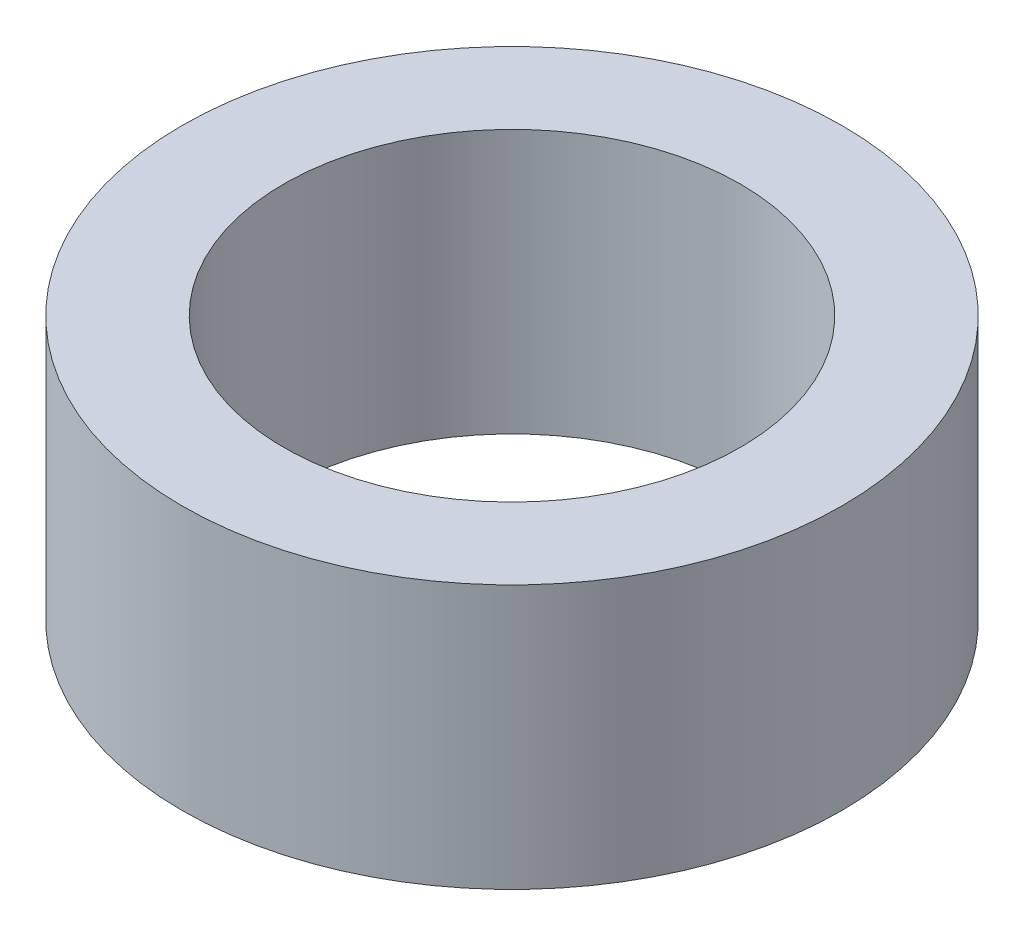
SolidWorks part; units mm, degrees
ref_plane "Front Plane" through (0, 0, 0) normal (0, 0, 1) x (1, 0, 0)
ref_plane "Top Plane" through (0, 0, 0) normal (0, 1, 0) x (1, 0, 0)
ref_plane "Right Plane" through (0, 0, 0) normal (1, 0, 0) x (0, 0, -1)
sketch "Sketch1" plane through (0, 0, 0) normal (0, 1, 0) x (1, 0, 0)
  circle A0 centre (0, 0) radius 32.5
  dimension "FLANGE_OD" = 65
extrude "Boss-Extrude1" add sketch "Sketch1" along normal blind 26
sketch "Sketch2" plane through (0, 0, 0) normal (0, 1, 0) x (1, 0, 0)
  circle A0 centre (0, 0) radius 22.5
  dimension "BORE_D" = 45
extrude "Cut-Extrude1" cut sketch "Sketch2" along normal through all
sketch "Sketch3" plane through (0, 26, 0) normal (0, 1, 0) x (1, 0, 0)
  circle A0 centre (0, 0) radius 13.7842 construction
  circle A1 centre (-13.7842, 0) radius 1.7098
  dimension "BOLT_D" = 3.4197
  dimension "BOLT_PCD" = 27.5684
extrude "Cut-Extrude2" cut sketch "Sketch3" against normal blind 17.3277 rebuild error yes
pattern_circular "CirPattern1" count 8 over 360 rebuild error yes
